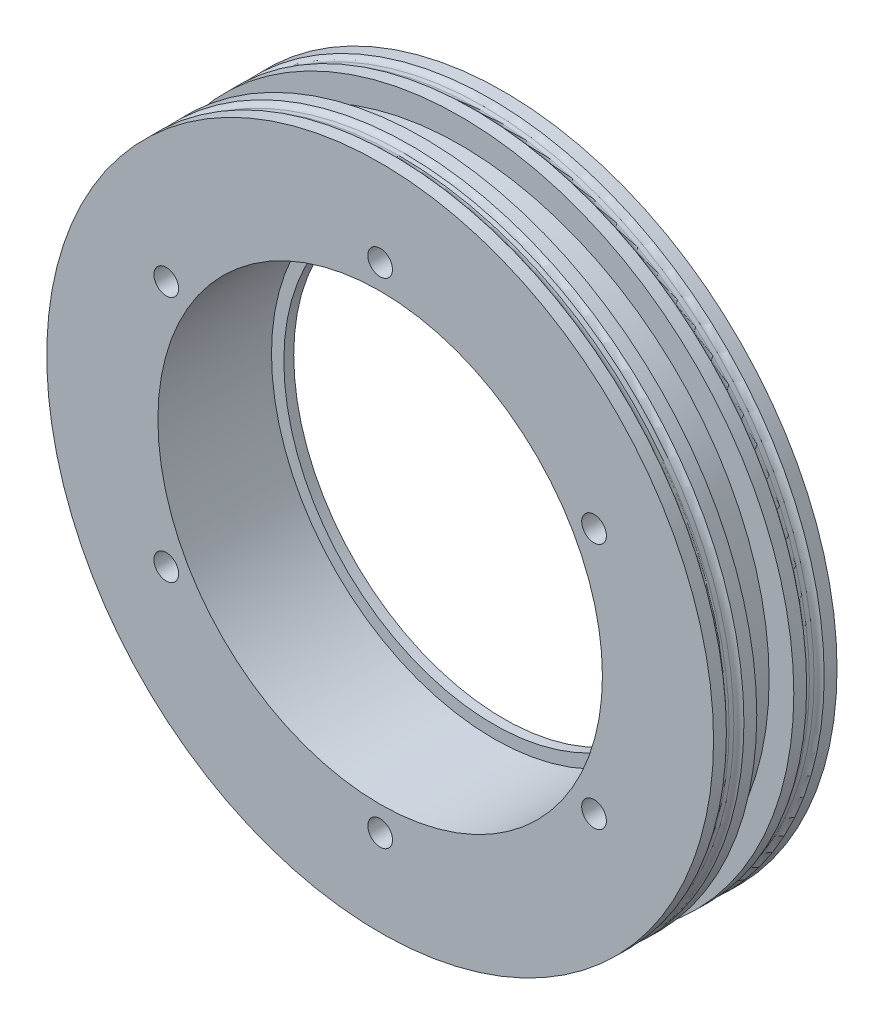
SolidWorks part; units mm, degrees
ref_plane "Front Plane" through (0, 0, 0) normal (0, 0, 1) x (1, 0, 0)
ref_plane "Top Plane" through (0, 0, 0) normal (0, 1, 0) x (1, 0, 0)
ref_plane "Right Plane" through (0, 0, 0) normal (1, 0, 0) x (0, 0, -1)
sketch "Sketch1" plane through (0, 0, 0) normal (0, 1, 0) x (1, 0, 0)
  line L0 (0, 0) -> (0, 42.0226) construction
  line L1 (45, 0) -> (45, 23)
  line L2 (45, 23) -> (42.5, 23)
  line L3 (42.5, 23) -> (42.5, 25)
  line L4 (42.5, 25) -> (67.5, 25)
  line L5 (67.5, 25) -> (67.5, 0)
  line L6 (67.5, 0) -> (45, 0)
  dimension "D1" = 90
  dimension "D2" = 135
  dimension "D3" = 23
  dimension "D4" = 85
  dimension "D5" = 2
revolve "Revolve1" add sketch "Sketch1" angle 360 about L0
hole_wizard "M6 Tapped Hole1" positions "Sketch2" profile "Sketch3" tap size "M6" standard "ISO"
sketch "Sketch2" plane through (0, 0, 0) normal (0, 0, 1) x (1, 0, 0)
  point P0 (0, 50)
  dimension "D1" = 50
sketch "Sketch3" plane through (0, 50, 0) normal (1, 0, 0) x (0, -1, 0)
  line L0 (0, 0) -> (0, 16.5022)
  line L1 (0, 16.5022) -> (2.5, 15)
  line L2 (2.5, 15) -> (2.5, 0)
  line L5 (2.5, 0) -> (0, 0)
  line L10 (0, 16.5022) -> (-2.5, 15) construction
  line L11 (0, -6.35) -> (0, 107.95) construction
  dimension "Tap Drill Dia." = 5
  dimension "Tap Drill Depth" = 15
  dimension "Drill Angle" = 118
cosmetic thread "Hole Thread1" parameters "D1"=12, "D2"=6
pattern_circular "CirPattern1" count 6 over 360 about axis through (0, 0, 0) along (0, 0, 1) of "M6 Tapped Hole1" reverse direction yes
sketch "Sketch4" plane through (0, 0, 0) normal (0, 1, 0) x (1, 0, 0)
  line L0 (-67.5, 0) -> (67.5, 0) construction
  line L1 (62.5, 16.25) -> (67.5, 16.25)
  line L2 (62.5, 16.25) -> (62.5, 8.75)
  line L3 (62.5, 8.75) -> (67.5, 8.75)
  line L4 (67.5, 16.25) -> (67.5, 8.75)
  line L5 (0, 0) -> (0, 16.25) construction
  point P4 (65, 8.75)
  dimension "D1" = 67.5
  dimension "D2" = 7.5
  dimension "D3" = 5
  dimension "D4" = 8.75
revolve "Cut-Revolve1" cut sketch "Sketch4" angle 360 about L5
sketch "Sketch5" plane through (0, 0, 0) normal (0, 1, 0) x (1, 0, 0)
  line L2 (67.5, 22.4) -> (67.5, 18.85)
  line L4 (66.75, 21.101) -> (66.75, 20.149)
  line L5 (67.5, 16.25) -> (67.5, 25) construction
  line L6 (64.0068, 25) -> (64.0068, 16.25) construction
  line L7 (67.5, 25) -> (-67.5, 25) construction
  line L8 (-67.5, 16.25) -> (67.5, 16.25) construction
  line L9 (64.0068, 20.625) -> (66.75, 20.625) construction
  line L10 (0, 0) -> (0, 25) construction
  line L11 (42.5, 25) -> (-42.5, 25) construction
  arc A0 (67.5, 22.4) -> (66.75, 21.101) centre (68.25, 21.101) ccw
  arc A1 (66.75, 20.149) -> (67.5, 18.85) centre (68.25, 20.149) ccw
  dimension "D3" = 3
  dimension "D1" = 3.55
  dimension "D2" = 66.75
revolve "Cut-Revolve2" cut sketch "Sketch5" angle 360 about L10
ref_plane "Plane1" through (0, 0, -12.5) normal (0, 0, 1) x (1, 0, 0)
mirror "Mirror1" about plane through (0, 0, -12.5) normal (0, 0, 1) of "Cut-Revolve2"
move or copy body "Body-Move/Copy1" [suppressed] bodies to move or copy 105
